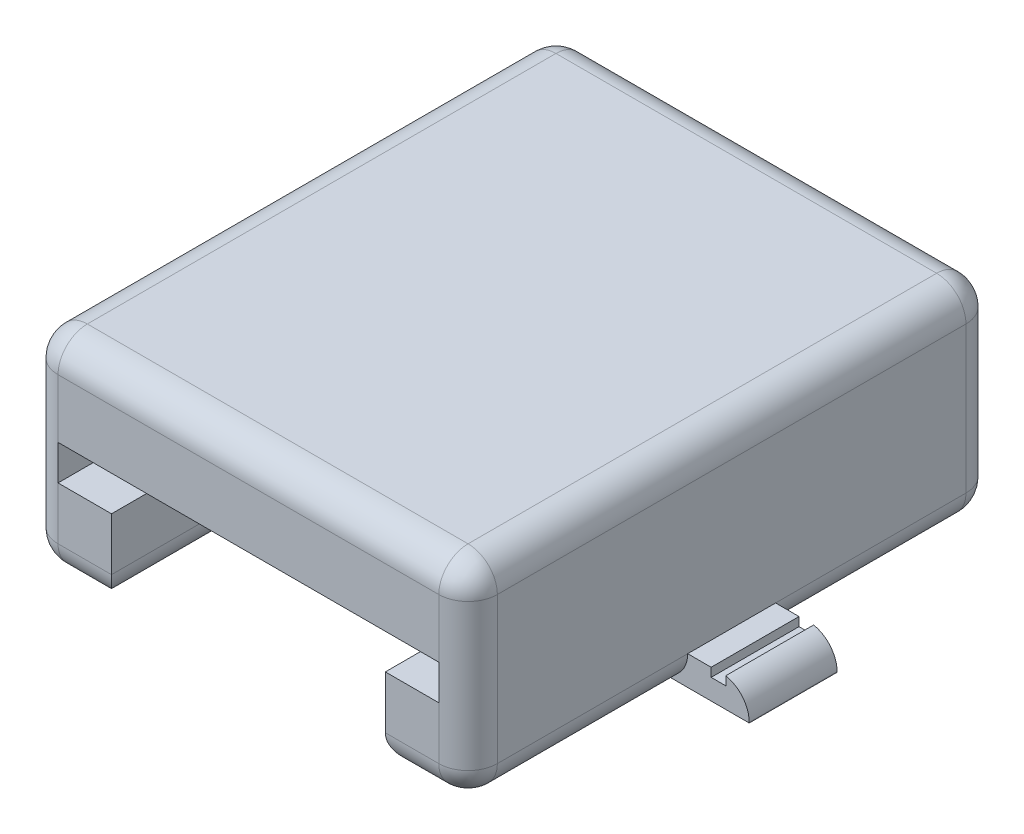
SolidWorks part; units mm, degrees
ref_plane "Front Plane" through (0, 0, 0) normal (0, 0, 1) x (1, 0, 0)
ref_plane "Top Plane" through (0, 0, 0) normal (0, 1, 0) x (1, 0, 0)
ref_plane "Right Plane" through (0, 0, 0) normal (1, 0, 0) x (0, 0, -1)
sketch "Sketch1" plane through (0, 0, 0) normal (0, 1, 0) x (1, 0, 0)
  line L1 (-7.5, -9) -> (7.5, -9)
  line L2 (-7.5, -9) -> (-7.5, 9)
  line L3 (-7.5, 9) -> (7.5, 9)
  line L4 (7.5, -9) -> (7.5, 9)
  line L5 (-7.5, -9) -> (7.5, 9) construction
  line L6 (-7.5, 9) -> (7.5, -9) construction
  point P0 (0, 0)
  dimension "D1" = 18
  dimension "D2" = 15
extrude "Boss-Extrude1" add sketch "Sketch1" along normal blind 7
sketch "Sketch2" plane through (0, 0, 9) normal (0, 0, 1) x (1, 0, 0)
  line L0 (-6.5, 0) -> (6.5, 0)
  line L1 (-7.5, 0) -> (7.5, 0) construction
  line L2 (6.5, 0) -> (6.5, 4)
  line L3 (6.5, 4) -> (-6.5, 4)
  line L4 (-6.5, 4) -> (-6.5, 0)
  line L5 (-6.5, 2.8) -> (6.5, 2.8)
  line L6 (-4.675, 2.8) -> (-4.675, 0)
  line L7 (0, 0) -> (0, 7) construction
  line L8 (-7.5, 7) -> (7.5, 7) construction
  line L9 (4.675, 2.8) -> (4.675, 0)
  line L10 (-0.475, 0) -> (-0.475, 5)
  line L11 (-0.475, 5) -> (0.475, 5)
  line L12 (0.475, 5) -> (0.475, 0)
  line L13 (0.775, 2.8) -> (0.775, 0)
  line L14 (-0.775, 2.8) -> (-0.775, 0)
  point P6 (0, 0)
  dimension "D1" = 4
  dimension "D2" = 1.2
  dimension "D3" = 9.35
  dimension "D4" = 0.95
  dimension "D5" = 0.3
  dimension "D6" = 13
extrude "Cut-Extrude1" cut sketch "Sketch2" against normal blind 14.2 contours L5 L10 L3 L4 | L3 L12 L5 L2 | L14 L5 L6 L0 | L5 L13 L4 L9 | L7 L0 L12 L5 | L4 L7 L5 L10 | L5 L7 L3 L10 | L7 L5 L12 L3 region at (-2.725, 1.4, 9) region at (-3.4875, 3.4, 9) region at (-0.2375, 1.4, 9) region at (-0.2375, 3.4, 9) region at (0.2375, 1.4, 9) region at (0.2375, 3.4, 9) region at (3.4875, 3.4, 9) region at (2.725, 1.4, 9)
sketch "Sketch8" plane through (0, 0, 9) normal (0, 0, 1) x (1, 0, 0)
  line L0 (-0.775, 2.8) -> (-0.475, 2.8)
  line L1 (-0.475, 2.8) -> (-0.475, 0)
  line L2 (-0.475, 0) -> (-0.775, 0)
  line L3 (-0.775, 0) -> (-0.775, 2.8)
  line L4 (0.475, 2.8) -> (0.775, 2.8)
  line L5 (0.775, 2.8) -> (0.775, 0)
  line L6 (0.775, 0) -> (0.475, 0)
  line L7 (0.475, 0) -> (0.475, 2.8)
extrude "Cut-Extrude4" cut sketch "Sketch8" against normal blind 10
sketch "Sketch9" plane through (-7.5, 0, 0) normal (-1, 0, 0) x (0, 0, 1)
  line L0 (-1.5, 0) -> (-1.5, 1)
  line L1 (9, 0) -> (-9, 0) construction
  line L2 (-1.5, 1) -> (1.5, 1)
  line L3 (1.5, 1) -> (1.5, 0)
  line L4 (-9, 0) -> (9, 0) construction
  line L5 (1.5, 0) -> (-1.5, 0)
  line L6 (-0.3093, 0) -> (0, 0) construction
  line L7 (0, 0) -> (0, 1) construction
  dimension "D1" = 3
  dimension "D2" = 1
extrude "Boss-Extrude2" add sketch "Sketch9" along normal blind 2.1
sketch "Sketch12" plane through (0, 0, 1.5) normal (0, 0, 1) x (1, 0, 0)
  line L0 (-8.55, 0) -> (-8.55, 1) construction
  line L1 (-9.6, 0) -> (-7.5, 0) construction
  line L2 (-9.6, 1) -> (-7.5, 1) construction
  dimension "D1" = 8.55
sketch "Sketch13" plane through (7.5, 0, 0) normal (1, 0, 0) x (0, 0, -1)
  line L0 (-1.5, 0) -> (-1.5, 1)
  line L1 (-1.5, 0) -> (-1.5, 1) construction
  line L2 (-1.5, 1) -> (1.5, 1)
  line L3 (1.5, 1) -> (1.5, 0)
  line L4 (9, 0) -> (-9, 0) construction
  line L5 (1.5, 0) -> (-1.5, 0)
  line L6 (0, 0) -> (0, 1) construction
  dimension "D1" = 3
  dimension "D2" = 1
extrude "Boss-Extrude3" add sketch "Sketch13" along normal blind 2.1
sketch "Sketch14" plane through (0, 0, 9) normal (0, 0, 1) x (1, 0, 0)
  line L0 (0, 0) -> (0, 7) construction
  line L1 (-7.5, 7) -> (7.5, 7) construction
  line L3 (9.6, 0) -> (7.5, 0) construction
  line L7 (8.55, 0) -> (8.55, 0.2814) construction
  line L12 (8.55, 0) -> (8.55, 1) construction
  line L13 (9.6, 1) -> (7.5, 1) construction
  line L14 (-8.8, 0.7) -> (-8.8, 1)
  line L15 (-8.3, 0.7) -> (-8.8, 0.7)
  line L16 (-8.3, 1) -> (-8.3, 0.7)
  line L17 (8.3, 1) -> (8.3, 0.7)
  line L18 (8.3, 0.7) -> (8.8, 0.7)
  line L19 (8.8, 0.7) -> (8.8, 1)
  line L20 (8.8, 1) -> (8.3, 1)
  line L21 (-8.8, 1) -> (-8.3, 1)
  dimension "D1" = 0.5
  dimension "D2" = 0.3
extrude "Cut-Extrude5" cut sketch "Sketch14" against normal blind 32.55
fillet "Fillet1" radius 1 19 edges at (0, 0, -9) (7.5, 0, -5.25) (-7.5, 0, -5.25) (-7.5, 0, 5.25) (7.5, 0, 5.25) (7.5, 7, 0) (9.6, 1, 0) (-9.6, 1, 0) (-7.5, 7, 0) (-7.5, 3.5, 9) (7.5, 3.5, 9) (6.0875, 0, 9) (4.675, 0, 1.9) (-4.675, 0, 1.9) (-6.0875, 0, 9) (0, 7, 9) (0, 7, -9) (7.5, 3.5, -9) (-7.5, 3.5, -9)
